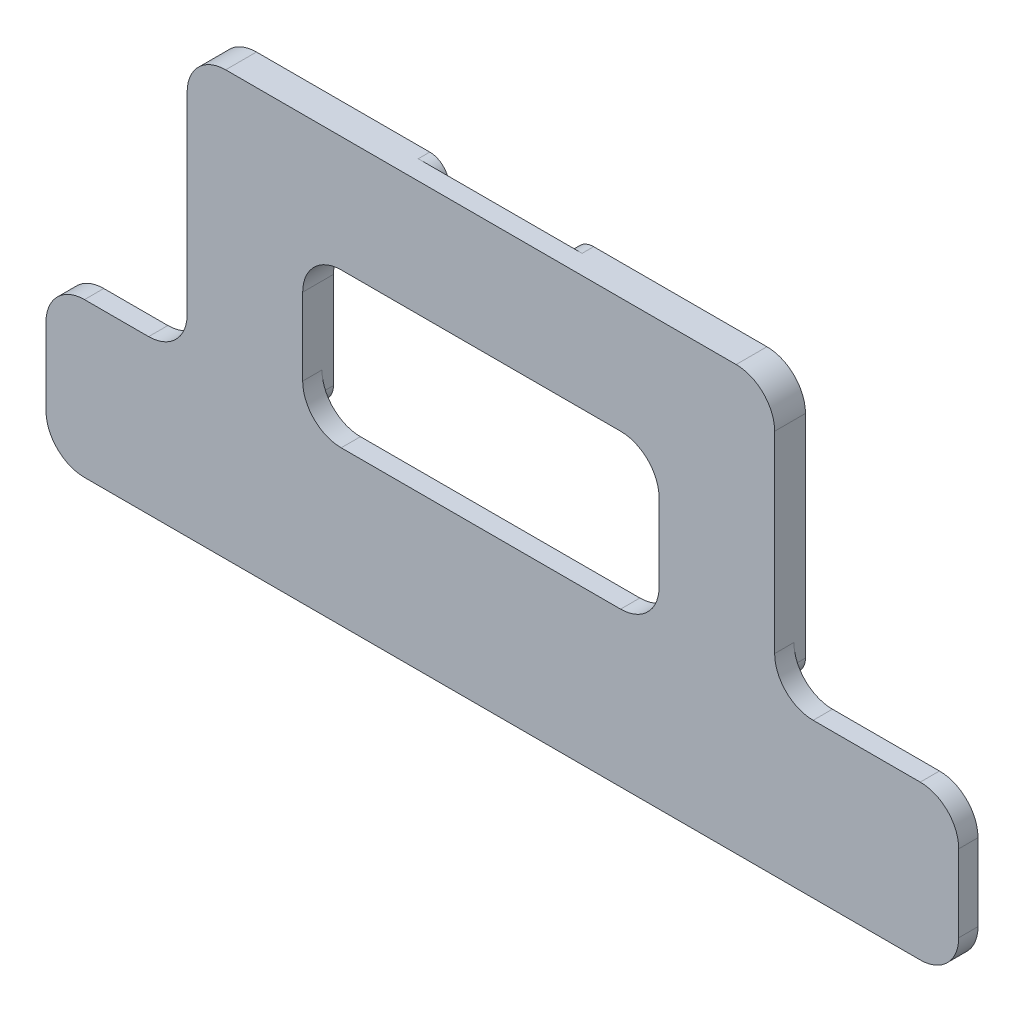
SolidWorks part; units mm, degrees
material "acero"
ref_plane "Alzado" through (0, 0, 0) normal (0, 0, 1) x (1, 0, 0)
ref_plane "Planta" through (0, 0, 0) normal (0, 1, 0) x (1, 0, 0)
ref_plane "Vista lateral" through (0, 0, 0) normal (1, 0, 0) x (0, 0, -1)
sketch "Croquis1" plane through (0, 0, 0) normal (0, 0, 1) x (1, 0, 0)
  line L0 (0, -3) -> (0, -408.9) construction
  line L1 (254.2, -341) -> (221.65, -341)
  line L2 (125, -381) -> (125, -421)
  line L3 (125, -421) -> (362, -421)
  line L4 (362, -381) -> (362, -421)
  line L5 (125, -381) -> (362, -381)
  line L6 (254.2, -311) -> (221.65, -311)
  line L7 (161.65, -311) -> (221.65, -311)
  line L9 (191.65, -341) -> (221.65, -341)
  line L10 (221.65, -311) -> (221.65, -341)
  line L11 (221.65, -376) -> (221.65, -257) construction
  line L12 (254.2, -257) -> (254.2, -376) construction
  line L13 (254.2, -311) -> (314.2, -311)
  line L14 (254.2, -311) -> (254.2, -341)
  line L15 (254.2, -341) -> (284.2, -341)
  line L21 (161.65, -381) -> (191.65, -381)
  line L23 (141.65, -381) -> (216.65, -381) construction
  line L26 (284.2, -341) -> (284.2, -381)
  line L27 (284.2, -381) -> (314.2, -381)
  line L28 (314.2, -311) -> (314.2, -381)
  line L29 (259.2, -381) -> (334.2, -381) construction
  line L30 (161.65, -311) -> (161.65, -381)
  line L31 (191.65, -341) -> (191.65, -381)
  dimension "D1" = 125
  dimension "D2" = 237
  dimension "D3" = 30
  dimension "D4" = 30
  dimension "D5" = 30
  dimension "D6" = 40
  dimension "D7" = 40
extrude "Saliente-Extruir1" add sketch "Croquis1" along normal blind 5 contours L28 L13 L14 L15 L26 L5 | L31 L9 L10 L7 L30 L5 | L5 L2 L3 L4 | L14 L6 L10 L1 region at (237.925, -326, 0) region at (290.2, -340, 0) region at (185.65, -340, 0) region at (243.5, -401, 0)
extrude "Saliente-Extruir2" add sketch "Croquis1<3>" against normal up to surface (3 mm away) contours L28 L13 L14 L15 L26 L5 | L31 L9 L10 L7 L30 L5 region at (290.2, -340, 0) region at (185.65, -340, 0)
sketch "Croquis1<3>" plane through (0, 0, 0) normal (0, 0, 1) x (1, 0, 0) same geometry as "Croquis1"
fillet "Redondeo1" radius 10 12 edges at (362, -421, 2.5) (362, -381, 2.5) (314.2, -311, 1) (314.2, -381, 2.5) (284.2, -381, 2.5) (284.2, -341, 1) (191.65, -341, 1) (161.65, -311, 1) (125, -421, 2.5) (125, -381, 2.5) (161.65, -381, 2.5) (191.65, -381, 2.5)
fillet "Redondeo2" radius 5 8 edges at (161.65, -381, -1.5) (191.65, -381, -1.5) (314.2, -381, -1.5) (284.2, -381, -1.5) (254.2, -311, -1.5) (254.2, -341, -1.5) (221.65, -341, -1.5) (221.65, -311, -1.5)
